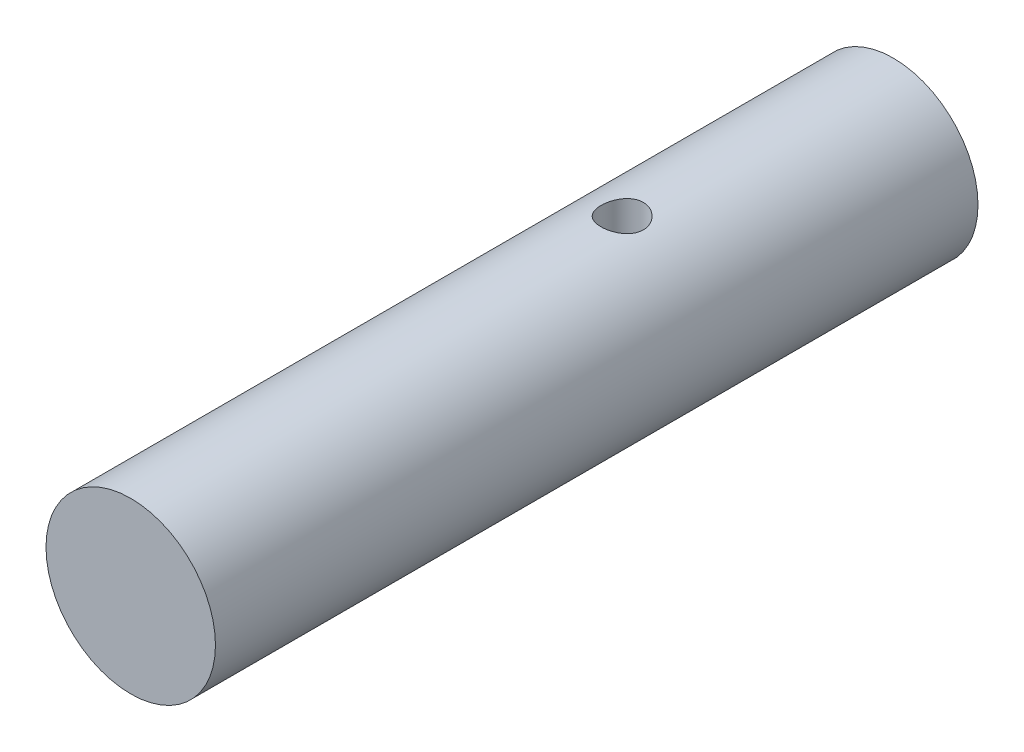
SolidWorks part; units mm, degrees
ref_plane "正面" through (0, 0, 0) normal (0, 0, 1) x (1, 0, 0)
ref_plane "平面" through (0, 0, 0) normal (0, 1, 0) x (1, 0, 0)
ref_plane "右側面" through (0, 0, 0) normal (1, 0, 0) x (0, 0, -1)
sketch "ｽｹｯﾁ2" plane through (0, 0, 0) normal (0, 0, 1) x (1, 0, 0)
  circle A0 centre (0, 0) radius 5
  dimension "D1" = 10
extrude "ﾎﾞｽ - 押し出し1" add sketch "ｽｹｯﾁ2" along normal blind 45
sketch "ｽｹｯﾁ3" plane through (0, 0, 0) normal (0, 1, 0) x (1, 0, 0)
  line L0 (0, 0) -> (0, -45) construction
  line L1 (-5, -45) -> (5, -45) construction
  line L2 (5, 0) -> (-5, 0) construction
  circle A0 centre (0, -16) radius 1.25
  dimension "D1" = 2.5
  dimension "D2" = 16
extrude "ｶｯﾄ - 押し出し1" cut sketch "ｽｹｯﾁ3" against normal through all both and the other way through all
